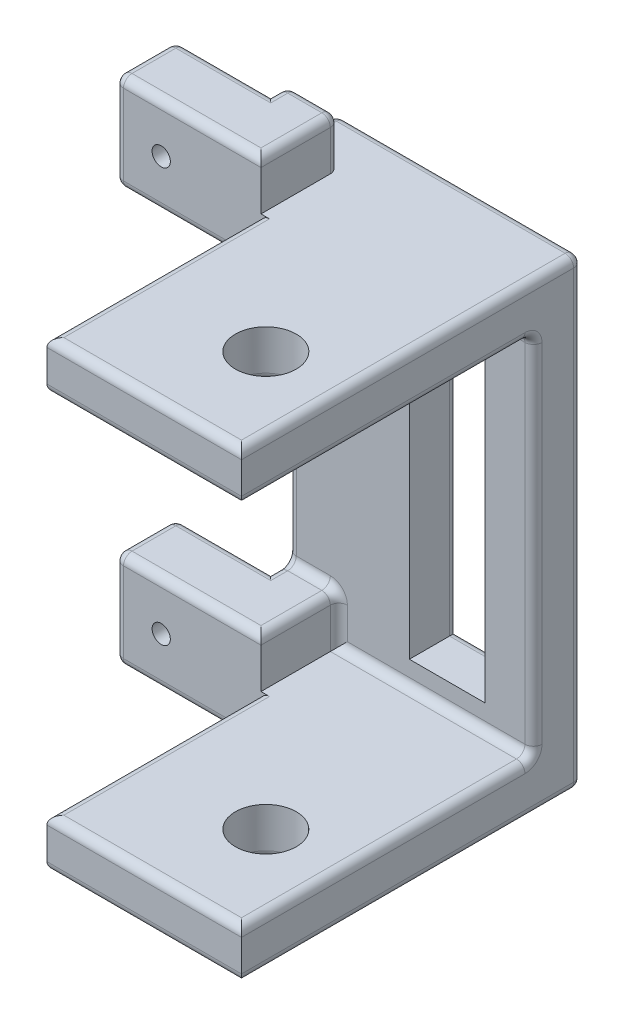
SolidWorks part; units mm, degrees
ref_plane "前视基准面" through (0, 0, 0) normal (0, 0, 1) x (1, 0, 0)
ref_plane "上视基准面" through (0, 0, 0) normal (0, 1, 0) x (1, 0, 0)
ref_plane "右视基准面" through (0, 0, 0) normal (1, 0, 0) x (0, 0, -1)
sketch "草图2" plane through (0, 0, 0) normal (0, 0, 1) x (1, 0, 0)
  line L3 (-5.9, -9.5) -> (6.1, -9.5)
  line L4 (6.1, 9.5) -> (6.1, -9.5)
  line L5 (0, 0) -> (2.4933, 0) construction
  line L6 (0, 0) -> (0, -3.9686) construction
  line L15 (-5.9, 9.5) -> (6.1, 9.5)
  line L20 (-5.9, 9.5) -> (-5.9, -9.5)
  line L21 (1, 6.5) -> (4.1, 6.5)
  line L23 (1, -6.5) -> (1, 6.5)
  line L26 (4.1, 6.5) -> (4.1, -6.5)
  line L28 (1, -6.5) -> (4.1, -6.5)
  point P0 (0, 0)
  dimension "D1" = 12
  dimension "D2" = 3.1
  dimension "D3" = 19
  dimension "D4" = 3
  dimension "D9" = 2
extrude "凸台-拉伸1" add sketch "草图2" along normal blind 2
sketch "草图3" plane through (0, 0, 2) normal (0, 0, 1) x (1, 0, 0)
  line L1 (-1.9, 9.5) -> (6.1, 9.5)
  line L2 (-1.9, 9.5) -> (-1.9, 7.5)
  line L3 (-1.9, 7.5) -> (6.1, 7.5)
  line L4 (6.1, 9.5) -> (6.1, 7.5)
  line L5 (6.1, -9.5) -> (6.1, 9.5) construction
  line L6 (-1.9, -7.5) -> (6.1, -7.5)
  line L8 (-1.9, -9.5) -> (6.1, -9.5)
  line L9 (6.1, -7.5) -> (6.1, -9.5)
  line L10 (-5.9, -9.5) -> (6.1, -9.5) construction
  line L11 (-1.9, -7.5) -> (-1.9, -9.5)
  line L12 (6.1, 9.5) -> (-5.9, 9.5) construction
  dimension "D1" = 2
  dimension "D2" = 2
  dimension "D3" = 8
  dimension "D4" = 8
extrude "凸台-拉伸2" add sketch "草图3" along normal blind 12
sketch "草图10" plane through (0, 0, 2) normal (0, 0, 1) x (1, 0, 0)
  line L9 (-7.9, 11.5) -> (-1.9, 11.5)
  line L10 (-7.9, 11.5) -> (-7.9, 7.5)
  line L11 (-7.9, 7.5) -> (-1.9, 7.5)
  line L12 (-1.9, 11.5) -> (-1.9, 7.5)
  line L13 (-7.9, -5.5) -> (-1.9, -5.5)
  line L14 (-7.9, -5.5) -> (-7.9, -9.5)
  line L15 (-7.9, -9.5) -> (-1.9, -9.5)
  line L16 (-1.9, -5.5) -> (-1.9, -9.5)
  line L17 (-1.9, -7.5) -> (-1.9, -9.5) construction
  line L19 (-1.9, 9.5) -> (-1.9, 7.5) construction
  line L20 (-1.9, 7.5) -> (6.1, 7.5) construction
  line L23 (-5.9, -9.5) -> (-1.9, -9.5) construction
  dimension "D1" = 4
  dimension "D2" = 6
extrude "凸台-拉伸4" add sketch "草图10" along normal blind 3.2
sketch "草图9" plane through (0, 0, 2) normal (0, 0, 1) x (1, 0, 0)
  line L3 (-7.9, 11.5) -> (-7.9, 7.5) construction
  line L4 (-6, 9.5) -> (-6, -7.5) construction
  line L5 (6.1, 9.5) -> (-1.9, 9.5) construction
  line L9 (6.1, -7.5) -> (-1.9, -7.5) construction
  circle A0 centre (-6, 9.5) radius 0.375
  circle A1 centre (-6, -7.5) radius 0.375
  point P10 (-10.8713, 1.8602)
  dimension "D1" = 0.75
  dimension "D2" = 0.75
  dimension "D4" = 1.9
extrude "切除-拉伸2" cut sketch "草图9" against normal up to next from surface starting at face at (-4.3, 9.5, 5.2)
sketch "草图11" plane through (0, -9.5, 0) normal (0, -1, 0) x (1, 0, 0)
  line L0 (-1.9, 14) -> (-1.9, 5.2) construction
  line L3 (-5.9, 0) -> (6.1, 0) construction
  circle A0 centre (3.1, 10) radius 1.25
  dimension "D1" = 2.5
  dimension "D2" = 5
  dimension "D3" = 10
extrude "切除-拉伸3" cut sketch "草图11" against normal through all
sketch "草图12" plane through (0, -9.5, 0) normal (0, -1, 0) x (1, 0, 0)
  line L0 (-7.9, 5.2) -> (-7.9, 2) construction
  line L1 (-7.9, 2.7) -> (-4, 2.7)
  line L2 (-7.9, 2.7) -> (-7.9, 0)
  line L3 (-7.9, 0) -> (-4, 0)
  line L4 (-4, 2.7) -> (-4, 0)
  line L5 (-5.9, 0) -> (6.1, 0) construction
  line L6 (-4.1, 2.6) -> (-7.9, 2.6) construction
  line L7 (-4.1, 0.1) -> (-4.1, 2.6) construction
  dimension "D1" = 0.1
  dimension "D2" = 0.1
extrude "切除-拉伸4" cut sketch "草图12" against normal up to next
fillet "圆角1" radius 0.35 54 edges at (-1.9, -6.5, 2) (6.1, 0, 2) (-4, 1, 2) (1, 0, 0) (2.55, 6.5, 0) (4.1, 0, 0) (2.55, -6.5, 0) (6.1, 0, 0) (1.05, 9.5, 0) (-4, 0, 0) (-4.9, -9.5, 5.2) (-1.9, -9.5, 9.6) (2.1, -9.5, 14) (6.1, -9.5, 7) (1.05, -9.5, 0) (-4, -9.5, 1.35) (-5.95, -9.5, 2.7) (3.1, -9.5, 8.75) (-1.9, -5.5, 3.6) (-4.9, -5.5, 5.2) (-5.95, -5.5, 2.7) (-4, -5.5, 2.35) (-2.95, -5.5, 2) (-7.9, -7.5, 5.2) (-7.9, -9.5, 3.95) (-7.9, -7.5, 2.7) (-7.9, -5.5, 3.95) (-4.9, 7.5, 5.2) (-1.9, 7.5, 9.6) (2.1, 7.5, 14) (6.1, 7.5, 8) (1.05, 7.5, 2) (-4, 7.5, 2.35) (-5.95, 7.5, 2.7) (1.85, 7.5, 10) (-2.95, 11.5, 2) (-1.9, 11.5, 3.6) (-4.9, 11.5, 5.2) (-5.95, 11.5, 2.7) (-4, 11.5, 2.35) (-7.9, 9.5, 5.2) (-7.9, 7.5, 3.95) (-7.9, 9.5, 2.7) (-7.9, 11.5, 3.95) (-4, 10.5, 2) (-1.9, 10.5, 2) (-4, 9.5, 1) (2.1, 9.5, 14) (6.1, 9.5, 7) (-1.9, 9.5, 9.6) (2.1, -7.5, 2) (6.1, -7.5, 8) (-1.9, -7.5, 9.6) (2.1, -7.5, 14)
